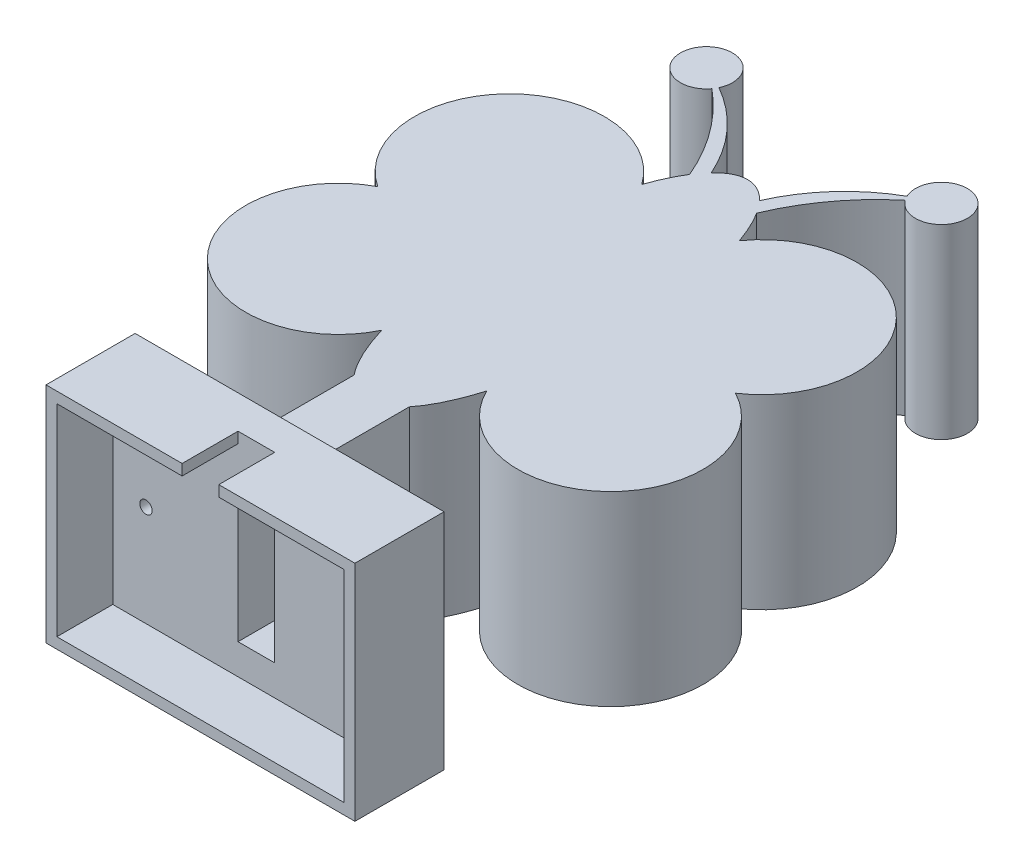
SolidWorks part; units mm, degrees
ref_plane "Front Plane" through (0, 0, 0) normal (0, 0, 1) x (1, 0, 0)
ref_plane "Top Plane" through (0, 0, 0) normal (0, 1, 0) x (1, 0, 0)
ref_plane "Right Plane" through (0, 0, 0) normal (1, 0, 0) x (0, 0, -1)
sketch "Sketch2" plane through (0, 0, 0) normal (0, 1, 0) x (1, 0, 0)
  line L0 (0, 61.5427) -> (0, -61.5427)
  line L1 (-8.8816, -56.3199) -> (8.8816, -56.3199)
  line L2 (-71.2697, 25.4882) -> (71.2697, 25.4882)
  line L3 (-8.8816, -86.0036) -> (-60.8682, -86.0036)
  line L4 (-8.8816, -56.3199) -> (8.8816, -56.3199)
  line L5 (-8.8816, -56.3199) -> (-8.8816, -86.0036)
  line L6 (-8.8816, -86.0036) -> (8.8816, -86.0036)
  line L7 (8.8816, -56.3199) -> (8.8816, -86.0036)
  line L8 (-60.8682, -86.0036) -> (-60.8682, -96.7074)
  line L9 (-60.8682, -96.7074) -> (60.8682, -96.7074)
  line L10 (8.8816, -86.0036) -> (60.8682, -86.0036)
  line L11 (60.8682, -96.7074) -> (60.8682, -86.0036)
  line L12 (8.8816, -86.0036) -> (-8.8816, -86.0036)
  arc A0 (-15.7093, 43.1478) -> (-57.5915, 0) centre (-40.683, 25.4882) ccw
  arc A1 (-57.5915, 0) -> (-16.9229, -39.4042) centre (-43.8209, -26.4765) ccw
  arc A2 (57.5915, 0) -> (16.9229, -39.4042) centre (43.8209, -26.4765) cw
  arc A3 (15.7093, 43.1478) -> (57.5915, 0) centre (40.683, 25.4882) cw
  arc A4 (-7.7773, 57.5803) -> (-37.8336, 86.0964) centre (-56.6364, 36.1801) ccw
  arc A5 (-10.798, 53.6435) -> (-37.8336, 86.0964) centre (-77.1059, 25.8919) ccw
  circle A6 centre (-37.8336, 86.0964) radius 8.3502
  arc A7 (10.798, 53.6435) -> (37.8336, 86.0964) centre (77.1059, 25.8919) cw
  arc A8 (7.7773, 57.5803) -> (37.8336, 86.0964) centre (56.6364, 36.1801) cw
  circle A9 centre (37.8336, 86.0964) radius 8.3502
  ellipse E0 centre (0, 0) end of major axis (0, 61.5427) minor radius 22.0308
  dimension "D1" = 123.0853
  dimension "D2" = 142.5393
extrude "Boss-Extrude1" add sketch "Sketch2" along normal blind 60 contours L9 L11 L10 L6 L3 L8 | E0 L5 L6 L7 | L1 E0 L2 L0 | E0 L1 L0 L2 | E0 L2 A0 A1 | E0 A0 L2 | E0 L2 A3 | E0 A2 A3 L2 | L2 E0 L0 | E0 L2 L0 | E0 A7 A9 A8 | A9 A7 A8 | A9 A8 A7 | E0 A4 A6 A5 | A5 A6 A4 | A4 A6 A5 region at (7.935, 0, -40.3472) region at (-7.935, 0, -40.3472) region at (9.9347, 0, 12.1312) region at (-9.9347, 0, 12.1312) region at (-17.3798, 0, -68.1368) region at (17.3798, 0, -68.1368) region at (-44.8789, 0, 14.6216) region at (-42.778, 0, -38.9947) region at (42.778, 0, -38.9947) region at (44.8789, 0, 14.6216) region at (-33.0513, 0, -83.358) region at (-37.9944, 0, -86.1884) region at (37.9944, 0, -86.1884) region at (33.0513, 0, -83.358) region at (0, 0, 72.8723) region at (0, 0, 91.3555)
extrude "Boss-Extrude2" add sketch "Sketch2<4>" along normal blind 60 contours L0 E0 L1 | L1 E0 L0 region at (3.3503, 0, 58.4168) region at (-3.3503, 0, 58.4168)
sketch "Sketch2<4>" plane through (0, 0, 0) normal (0, 1, 0) x (1, 0, 0) same geometry as "Sketch2"
sketch "Sketch5" plane through (0, 0, 96.7074) normal (0, 0, 1) x (1, 0, 0)
  line L0 (0, 60) -> (0, 0)
  line L1 (-8.8816, 60) -> (8.8816, 60)
  line L2 (-8.8816, 60) -> (-8.8816, 0)
  line L3 (-8.8816, 0) -> (8.8816, 0)
  line L4 (8.8816, 60) -> (8.8816, 0)
  line L5 (0, 53.3223) -> (5.9045, 53.3223)
  line L6 (5.9045, 53.3223) -> (5.9045, 7.2858)
  line L7 (5.9045, 7.2858) -> (0, 7.2858)
  line L8 (0, 7.2858) -> (-5.9045, 7.2858)
  line L9 (-5.9045, 7.2858) -> (-5.9045, 53.3223)
  line L10 (-5.9045, 53.3223) -> (0, 53.3223)
extrude "Cut-Extrude1" cut sketch "Sketch5" against normal blind 96 contours L7 L6 L5 L0 | L10 L9 L8 L0 region at (2.9522, 30.304, 96.7074) region at (-2.9522, 30.304, 96.7074)
sketch "Sketch6" plane through (0, 60, 0) normal (0, 1, 0) x (1, 0, 0)
  line L1 (-60.8682, -86.0036) -> (60.8682, -86.0036)
  line L2 (-60.8682, -86.0036) -> (-60.8682, -96.7074)
  line L3 (-60.8682, -96.7074) -> (60.8682, -96.7074)
  line L4 (60.8682, -86.0036) -> (60.8682, -96.7074)
extrude "Boss-Extrude5" add sketch "Sketch6" along normal blind 6
sketch "Sketch8" plane through (0, 0, 0) normal (0, -1, 0) x (1, 0, 0)
  line L1 (-60.8682, 96.7074) -> (60.8682, 96.7074)
  line L2 (-60.8682, 96.7074) -> (-60.8682, 86.0036)
  line L3 (-60.8682, 86.0036) -> (60.8682, 86.0036)
  line L4 (60.8682, 96.7074) -> (60.8682, 86.0036)
extrude "Boss-Extrude6" add sketch "Sketch8" along normal blind 6
sketch "Sketch9" plane through (60.8682, 0, 0) normal (1, 0, 0) x (0, 0, -1)
  line L1 (-96.7074, 66) -> (-86.0036, 66)
  line L2 (-96.7074, 66) -> (-96.7074, -6)
  line L3 (-96.7074, -6) -> (-86.0036, -6)
  line L4 (-86.0036, 66) -> (-86.0036, -6)
extrude "Cut-Extrude2" cut sketch "Sketch9" against normal blind 11.12
sketch "Sketch10" plane through (-60.8682, 0, 0) normal (-1, 0, 0) x (0, 0, 1)
  line L1 (86.0036, 66) -> (96.7074, 66)
  line L2 (86.0036, 66) -> (86.0036, -6)
  line L3 (86.0036, -6) -> (96.7074, -6)
  line L4 (96.7074, 66) -> (96.7074, -6)
extrude "Cut-Extrude3" cut sketch "Sketch10" against normal blind 11.12
sketch "Sketch11" plane through (0, 0, 96.7074) normal (0, 0, 1) x (1, 0, 0)
  line L1 (-49.7482, 66) -> (-46.2482, 66)
  line L2 (-49.7482, 66) -> (-49.7482, 62.5)
  line L3 (-49.7482, 62.5) -> (-46.2482, 62.5)
  line L4 (-46.2482, 66) -> (-46.2482, 62.5)
  line L5 (49.7482, -6) -> (46.2482, -6)
  line L6 (49.7482, -6) -> (49.7482, -2.5)
  line L7 (49.7482, -2.5) -> (46.2482, -2.5)
  line L8 (46.2482, -6) -> (46.2482, -2.5)
  line L9 (-46.2482, 62.5) -> (46.2482, 62.5)
  line L10 (-46.2482, 62.5) -> (-46.2482, -2.5)
  line L11 (-46.2482, -2.5) -> (46.2482, -2.5)
  line L12 (46.2482, 62.5) -> (46.2482, -2.5)
  line M9 (-49.7482, 66) -> (-49.7482, -6)
  line M10 (-49.7482, -6) -> (49.7482, -6)
  line M11 (49.7482, -6) -> (49.7482, 66)
  line M12 (49.7482, 66) -> (-49.7482, 66)
  dimension "D1" = 3.5
  dimension "D2" = 3.5
  dimension "D3" = 3.5
  dimension "D4" = 3.5
extrude "Boss-Extrude7" add sketch "Sketch11" along normal blind 18 contours L9 L12 L7 L4 M11 M12 | L11 L10 L3 L8 M9 M10 | L4 L3 M12 M9 | L8 L7 M10 M11 region at (-47.9982, 64.25, 96.7074) region at (1.75, 64.8207, 96.7074) region at (-47.9982, 61.3207, 96.7074) region at (47.9982, -4.25, 96.7074)
sketch "Sketch12" plane through (0, 0, 96.7074) normal (0, 0, 1) x (1, 0, 0)
  line L0 (-5.9045, 53.3223) -> (-5.9045, 62.5)
  line L1 (-46.2482, 62.5) -> (46.2482, 62.5) construction
  line L2 (5.9045, 53.3223) -> (5.9045, 62.5)
sketch "Sketch13" plane through (0, 62.5, 0) normal (0, -1, 0) x (1, 0, 0)
  line L0 (-5.9045, 96.7074) -> (-5.9045, 114.7074)
  line L1 (-46.2482, 114.7074) -> (46.2482, 114.7074) construction
  line L2 (5.9045, 96.7074) -> (5.9045, 114.7074)
  line L3 (-5.9045, 114.7074) -> (5.9045, 114.7074)
  line L4 (-5.9045, 96.7074) -> (5.9045, 96.7074)
extrude "Cut-Extrude4" cut sketch "Sketch13" against normal blind 18
sketch "Sketch14" plane through (0, 0, 96.7074) normal (0, 0, 1) x (1, 0, 0)
  line L0 (-46.2482, 62.5) -> (-46.2482, -2.5)
  line L1 (-46.2482, 30) -> (-35.5482, 30)
  circle A0 centre (-35.5482, 30) radius 2
  dimension "D1" = 10.7
extrude "Cut-Extrude5" cut sketch "Sketch14" against normal up to next contours A0 region at (-35.5482, 28.0566, 96.7074)
